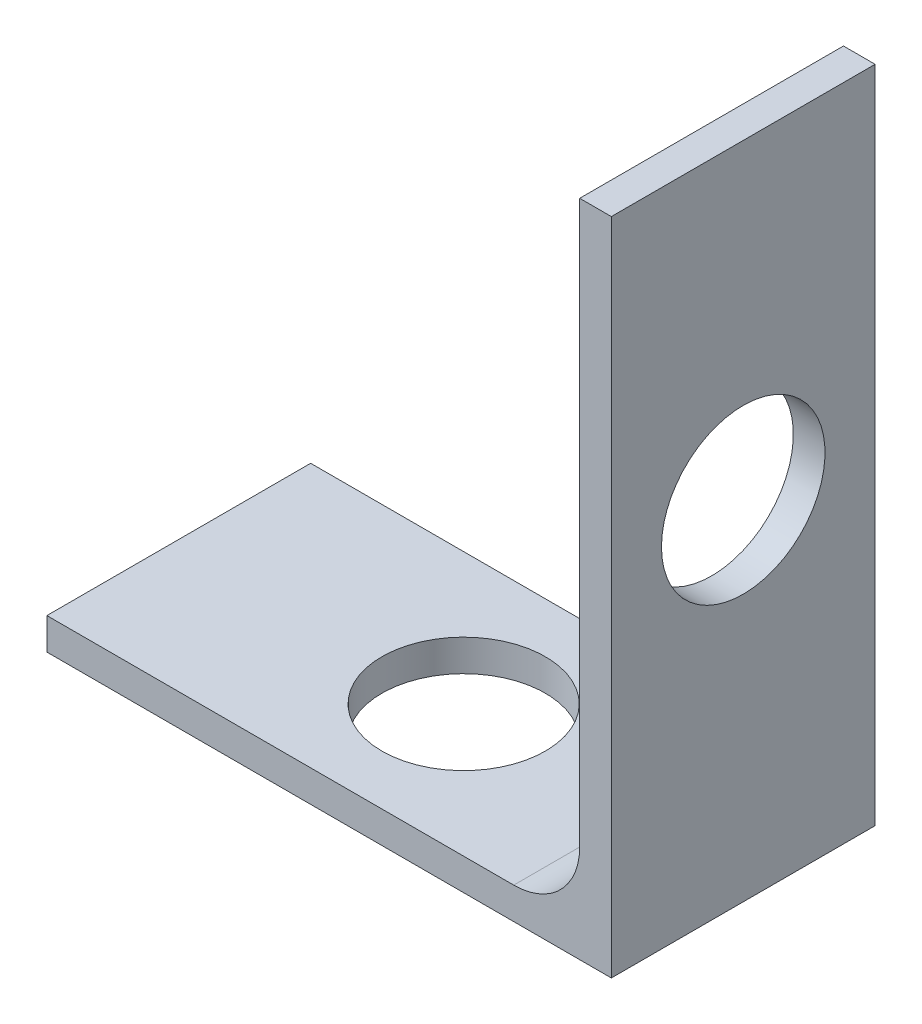
SolidWorks part; units mm, degrees
material "1060 Alloy"
ref_plane "Front Plane" through (0, 0, 0) normal (0, 0, 1) x (1, 0, 0)
ref_plane "Top Plane" through (0, 0, 0) normal (0, 1, 0) x (1, 0, 0)
ref_plane "Right Plane" through (0, 0, 0) normal (1, 0, 0) x (0, 0, -1)
sketch "Sketch1" plane through (0, 0, 0) normal (0, 0, 1) x (1, 0, 0)
  line L0 (0, 0) -> (27.178, 0)
  line L1 (27.178, 0) -> (27.178, 31.75)
  line L2 (0, 0) -> (0, 1.524)
  line L3 (0, 1.524) -> (25.654, 1.524)
  line L4 (25.654, 1.524) -> (25.654, 31.75)
  line L5 (25.654, 31.75) -> (27.178, 31.75)
  dimension "Height" = 31.75
  dimension "Depth" = 27.178
  dimension "Width2" = 1.524
  dimension "Width1" = 1.524
extrude "Boss-Extrude1" add sketch "Sketch1" along normal blind 12.7
sketch "Sketch2" plane through (25.654, 0, 0) normal (-1, 0, 0) x (0, 0, 1)
  line L8 (0, 31.75) -> (0, 1.524) construction
  line L9 (12.7, 0) -> (0, 0) construction
  circle A0 centre (6.35, 16.764) radius 3.937
  point P8 (6.35, 17.5578)
  dimension "SideHoleDiameter" = 7.874
  dimension "SideHoleHorizontal" = 6.35
  dimension "SideHoleVertical" = 16.764
extrude "Cut-Extrude1" cut sketch "Sketch2" against normal blind 6.35
sketch "Sketch4" plane through (0, 1.524, 0) normal (0, 1, 0) x (1, 0, 0)
  line L0 (25.654, -12.7) -> (25.654, 0) construction
  line L6 (25.654, 0) -> (0, 0) construction
  circle A0 centre (13.716, -6.35) radius 3.937
  dimension "D1" = 7.874
  dimension "BottomHoleHorizontal" = 11.938
  dimension "BottomHoleVertical" = 6.35
extrude "Cut-Extrude2" cut sketch "Sketch4" against normal blind 6.35
fillet "Fillet2" radius 3.175 1 edges at (25.654, 1.524, 6.35) type face fillet first side face at (25.654, 16.764, 10.287) second side face at (13.716, 1.524, 10.287)
equation "\"height\"=1.25"
equation "\"width\"= .06in"
equation "\"depth\"= 1.07in"
equation "\"extrusion\"= .5in"
equation "\"side hole diameter\" = .31in"
equation "\"horizontal side hole\"= .25in"
equation "\"vertical side hole\" = .66in"
equation "\"bottom hole diameter\" = .31in"
equation "\"horizontal bottom hole\"= .47in"
equation "\"vertical bottom hole\"= .25in"
